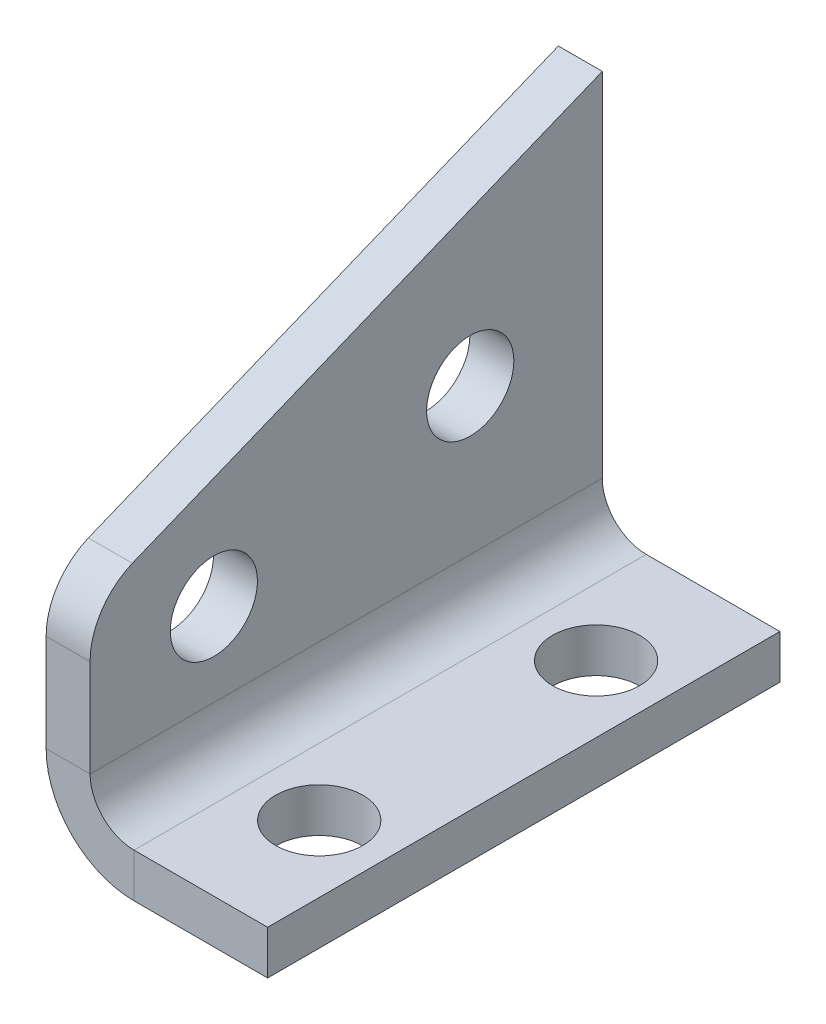
SolidWorks part; units mm, degrees
note: The reader was unsure of these and kept them because the rebuilt part matched: flange length of "Edge-Flange1".
ref_plane "Front Plane" through (0, 0, 0) normal (0, 0, 1) x (1, 0, 0)
ref_plane "Top Plane" through (0, 0, 0) normal (0, 1, 0) x (1, 0, 0)
ref_plane "Right Plane" through (0, 0, 0) normal (1, 0, 0) x (0, 0, -1)
sketch "Sketch1" plane through (0, 0, 0) normal (1, 0, 0) x (0, 0, -1)
  line L0 (71.7184, 2.1678) -> (102.9942, 47.6694)
  line L1 (0, 0) -> (95.6245, 0)
  line L5 (74.7808, 82.752) -> (14.6027, 58.2976)
  line L6 (11.5511, 53.6652) -> (11.5511, 40.2912)
  line L7 (11.5511, 40.2912) -> (48.3501, 40.2912)
  line L8 (50.1591, 38.5003) -> (50.1591, 0)
  line L9 (50.1591, 0) -> (67.5979, 0)
  line L10 (56.6677, 37) -> (96.5316, 37)
  line L11 (48.5511, 46.2861) -> (48.5511, 71.7841)
  arc A0 (67.5979, 0) -> (71.7184, 2.1678) centre (67.5979, 5) ccw
  arc A1 (102.9942, 47.6694) -> (74.7808, 82.752) centre (83.6279, 60.9809) ccw
  arc A2 (14.6027, 58.2976) -> (11.5511, 53.6652) centre (16.551, 53.6928) ccw
  arc A3 (50.1591, 38.5003) -> (48.3501, 40.2912) centre (48.3591, 38.4912) ccw
  circle A4 centre (20.4902, 52.6725) radius 3.15
  circle A5 centre (39.0112, 57.1948) radius 3.15
  circle A6 centre (66.345, 9.2223) radius 3.2825
  circle A7 centre (73.0099, 28.4056) radius 3.2825
  circle A8 centre (83.6279, 42.4814) radius 1.75
  circle A9 centre (102.3808, 60.9809) radius 1.75
  circle A10 centre (83.6279, 79.4804) radius 1.75
  circle A11 centre (83.6279, 60.9809) radius 13.8
  circle A12 centre (65.3817, 60.9809) radius 1.75
  dimension "D3" = 1.8
  dimension "D4" = 23.5
  dimension "D5" = 27.6
  dimension "D6" = 3.5
  dimension "D7" = 6.3
  dimension "D1" = 37
  dimension "D2" = 37
sketch "Sketch2" plane through (0, 0, 0) normal (1, 0, 0) x (0, 0, -1)
  line L0 (48.5511, 46.2861) -> (48.5511, 71.7841) construction
  line L1 (48.5511, 40.2912) -> (48.5511, 72.0931)
  line L2 (11.5511, 40.2912) -> (48.3501, 40.2912) construction
  line L3 (11.5511, 53.6652) -> (11.5511, 40.2912) construction
  line L4 (74.7808, 82.752) -> (14.6027, 58.2976) construction
  line L5 (11.5511, 40.2912) -> (48.5511, 40.2912)
  line L6 (11.5511, 53.6652) -> (11.5511, 40.2912)
  line L7 (48.5511, 72.0931) -> (14.6027, 58.2976)
  circle A0 centre (39.0112, 57.1948) radius 3.15 construction
  circle A1 centre (20.4902, 52.6725) radius 3.15 construction
  arc A2 (14.6027, 58.2976) -> (11.5511, 53.6652) centre (16.551, 53.6928) ccw construction
  circle A3 centre (39.0112, 57.1948) radius 3.15
  circle A4 centre (20.4902, 52.6725) radius 3.15
  arc A5 (14.6027, 58.2976) -> (11.5511, 53.6652) centre (16.551, 53.6928) ccw
  point P0 (11.5511, 40.2912)
base flange "Base-Flange1" sketch "Sketch2" thickness 3.175 reverse thickness direction no parameters "D1"=3.175
edge flange "Edge-Flange1" sketch "Sketch9" flange angle 90 flange length 12.825 flange position material inside bend radius 3.175 thickness 3.175 relief rectangular parameters "D6"=10
sketch "Sketch9" plane through (0, 40.2912, 0) normal (0, -1, 0) x (0, 0, -1)
  line L0 (11.5511, 0) -> (48.5511, 0) construction
  line L1 (11.5511, 0) -> (48.5511, 0)
  line L2 (11.5511, 0) -> (11.5511, 12.825)
  line L3 (11.5511, 12.825) -> (48.5511, 12.825)
  line L4 (48.5511, 12.825) -> (48.5511, 0)
bend "EdgeBend1" bend radius 3.175 bend angle 90 parameters "D5"=1
sketch "Sketch10" plane through (0, 43.4662, 0) normal (0, 1, 0) x (1, 0, 0)
  line L0 (12.825, 30.0511) -> (3.175, 30.0511) construction
  line L1 (12.825, 48.5511) -> (12.825, 11.5511) construction
  line L2 (3.175, 11.5511) -> (3.175, 48.5511) construction
  line L3 (8, 30.0511) -> (8, 40.1023) construction
  line L4 (8, 30.0511) -> (8, 20.1023) construction
  circle A0 centre (8, 40.1023) radius 3.15
  circle A1 centre (8, 20.1023) radius 3.15
  dimension "D1" = 6.3
extrude "Cut-Extrude1" cut sketch "Sketch10" against normal blind 10 normal cut yes
sketch "Bend-Lines1" [suppressed] plane through (0, 0, 0) normal (0, 1, 0) x (1, 0, 0)
sketch "Bounding-Box1" [suppressed] plane through (0, 0, 0) normal (0, 1, 0) x (1, 0, 0)
sheet metal parameters "Sheet-Metal1" thickness 3.175 parameters "D1"=3.175
flat pattern "Flat-Pattern1" [suppressed]
sketch "Bend-Lines2" plane through (0, 0, 0) normal (0, 1, 0) x (1, 0, 0)
sketch3d "Bounding-Box2" [suppressed]
  line L0 (4.9999, 18.4003, 0) -> (-32.0001, 18.4003, 0) construction
  line L1 (4.9999, -13.4016, 0) -> (-32.0001, -13.4016, 0) construction
  line L2 (4.9999, 18.4003, 0) -> (4.9999, -13.4016, 0) construction
  line L3 (-32.0001, 18.4003, 0) -> (-32.0001, -13.4016, 0) construction
sheet metal parameters "Sheet-Metal2" thickness 3.175 parameters "D1"=3.175
flat pattern "Flat-Pattern1"
sketch "Bend-Lines2" plane through (0, 0, 0) normal (1, 0, 0) x (0, 0, -1)
  line L0 (11.5511, 45.0537) -> (48.5511, 45.0537) construction
  line L1 (11.5511, 45.0537) -> (48.5511, 45.0537) construction
sketch3d "Bounding-Box2" [suppressed]
  line L0 (32.0001, -19.8766, 0) -> (32.0001, 18.4003, 0) construction
  line L1 (-4.9999, -19.8766, 0) -> (-4.9999, 18.4003, 0) construction
  line L2 (32.0001, -19.8766, 0) -> (-4.9999, -19.8766, 0) construction
  line L3 (32.0001, 18.4003, 0) -> (-4.9999, 18.4003, 0) construction
bend of the flat pattern "Flatten-<EdgeBend1>1"
sheet metal parameters "Sheet-Metal3" thickness 3.175 parameters "D1"=3.175
flat pattern "Flat-Pattern1"
sketch "Bend-Lines2" plane through (0, 0, 0) normal (1, 0, 0) x (0, 0, -1)
  line L0 (11.5511, 45.0537) -> (48.5511, 45.0537) construction
  line L1 (11.5511, 45.0537) -> (48.5511, 45.0537) construction
sketch3d "Bounding-Box2" [suppressed]
  line L0 (32.0001, -19.8766, 0) -> (32.0001, 18.4003, 0) construction
  line L1 (-4.9999, -19.8766, 0) -> (-4.9999, 18.4003, 0) construction
  line L2 (32.0001, -19.8766, 0) -> (-4.9999, -19.8766, 0) construction
  line L3 (32.0001, 18.4003, 0) -> (-4.9999, 18.4003, 0) construction
bend of the flat pattern "Flatten-<EdgeBend1>1"
